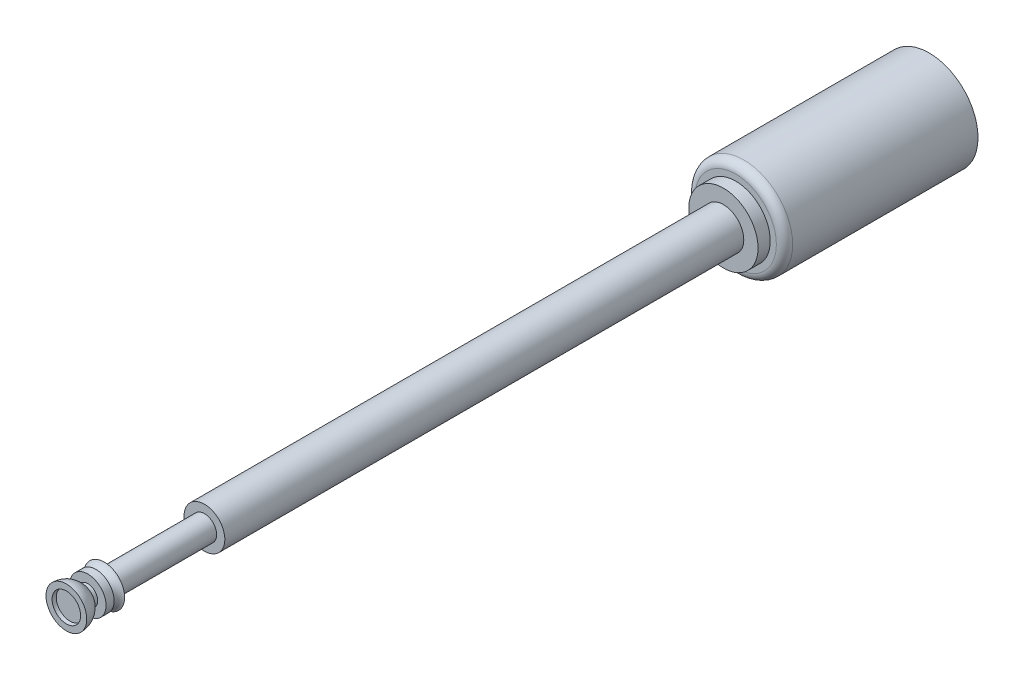
SolidWorks part; units mm, degrees
ref_plane "Front Plane" through (0, 0, 0) normal (0, 0, 1) x (1, 0, 0)
ref_plane "Top Plane" through (0, 0, 0) normal (0, 1, 0) x (1, 0, 0)
ref_plane "Right Plane" through (0, 0, 0) normal (1, 0, 0) x (0, 0, -1)
sketch "Sketch1" plane through (0, 0, 0) normal (0, 0, 1) x (1, 0, 0)
  circle A0 centre (0, 0) radius 0.5
  circle A1 centre (0, 0) radius 1.2
  dimension "D1" = 1
  dimension "D2" = 2.4
extrude "Boss-Extrude1" add sketch "Sketch1" along normal blind 15.5 contours A0
extrude "Boss-Extrude2" add sketch "Sketch1<3>" against normal blind 4.75 separate body contours A1 A0 | A0 region at (-1.1661, 0, 0)
sketch "Sketch1<3>" plane through (0, 0, 0) normal (0, 0, 1) x (1, 0, 0) same geometry as "Sketch1"
fillet "Fillet1" radius 0.2 1 edges at (1.2, 0, 0)
sketch "Sketch2" plane through (0, 0, 0) normal (0, 0, 1) x (1, 0, 0)
  circle A0 centre (0, 0) radius 0.85
  dimension "D1" = 1.7
extrude "Boss-Extrude3" add sketch "Sketch2" along normal blind 0.3
sketch "Sketch3" plane through (0, 0, 0) normal (0, 1, 0) x (1, 0, 0)
  line L0 (0.5, -15.5) -> (0, -15.5)
  line L1 (-0.5, -15.5) -> (0.5, -15.5) construction
  line L2 (0, -15.5) -> (0, -16.08)
  line L3 (0.35, -16.43) -> (0.5, -16.43)
  line L4 (0.243, -15.993) -> (0.243, -15.9033)
  line L5 (0.243, -15.9033) -> (0.4476, -15.9033)
  line L6 (0.4476, -15.9033) -> (0.4476, -15.7059)
  line L7 (0.4476, -15.7059) -> (0.3695, -15.7059)
  arc A0 (0, -16.08) -> (0.35, -16.43) centre (0, -16.43) cw
  arc A1 (0.5, -16.43) -> (0.243, -15.993) centre (0, -16.43) ccw
  arc A2 (0.3695, -15.7059) -> (0.5, -15.5) centre (0.5971, -15.7059) cw
  dimension "D2" = 0.35
  dimension "D3" = 0.5
  dimension "D1" = 0.93
revolve "Revolve1" add sketch "Sketch3" angle 360 about L2
sketch "Sketch4" plane through (0, 0, 0) normal (0, 1, 0) x (1, 0, 0)
  line L0 (0, -15.5) -> (0, -16.43) construction
  line L1 (0.5, -15.5) -> (-0.5, -15.5) construction
  line L2 (-0.5, -16.43) -> (0.5, -16.43) construction
  line L4 (0, -16.2947) -> (-0.4615, -16.2947)
  line L5 (0, -16.2947) -> (0, -16.34)
  line L6 (0, -16.34) -> (-0.4615, -16.34)
  line L7 (-0.4615, -16.2947) -> (-0.4615, -16.34)
  dimension "D1" = 0.84
revolve "Revolve2" add sketch "Sketch4" angle 360 about L0
sketch "Sketch7" plane through (0, 0, 0) normal (0, 1, 0) x (1, 0, 0)
  line L0 (0.5, -15.5) -> (-0.5, -15.5) construction
  line L1 (-0.3, -15.5) -> (-0.9007, -15.5)
  line L2 (-0.3, -15.5) -> (-0.3, -13.04)
  line L3 (-0.3, -13.04) -> (-0.9007, -13.04)
  line L4 (-0.9007, -15.5) -> (-0.9007, -13.04)
  line L5 (0, -15.5) -> (0, -16.8618) construction
  dimension "D1" = 2.46
  dimension "D2" = 0.3
revolve "Cut-Revolve1" cut sketch "Sketch7" angle 360 about L5
sketch "Sketch10" plane through (0, 0, -4.75) normal (0, 0, -1) x (-1, 0, 0)
  point P0 (0, 0)
